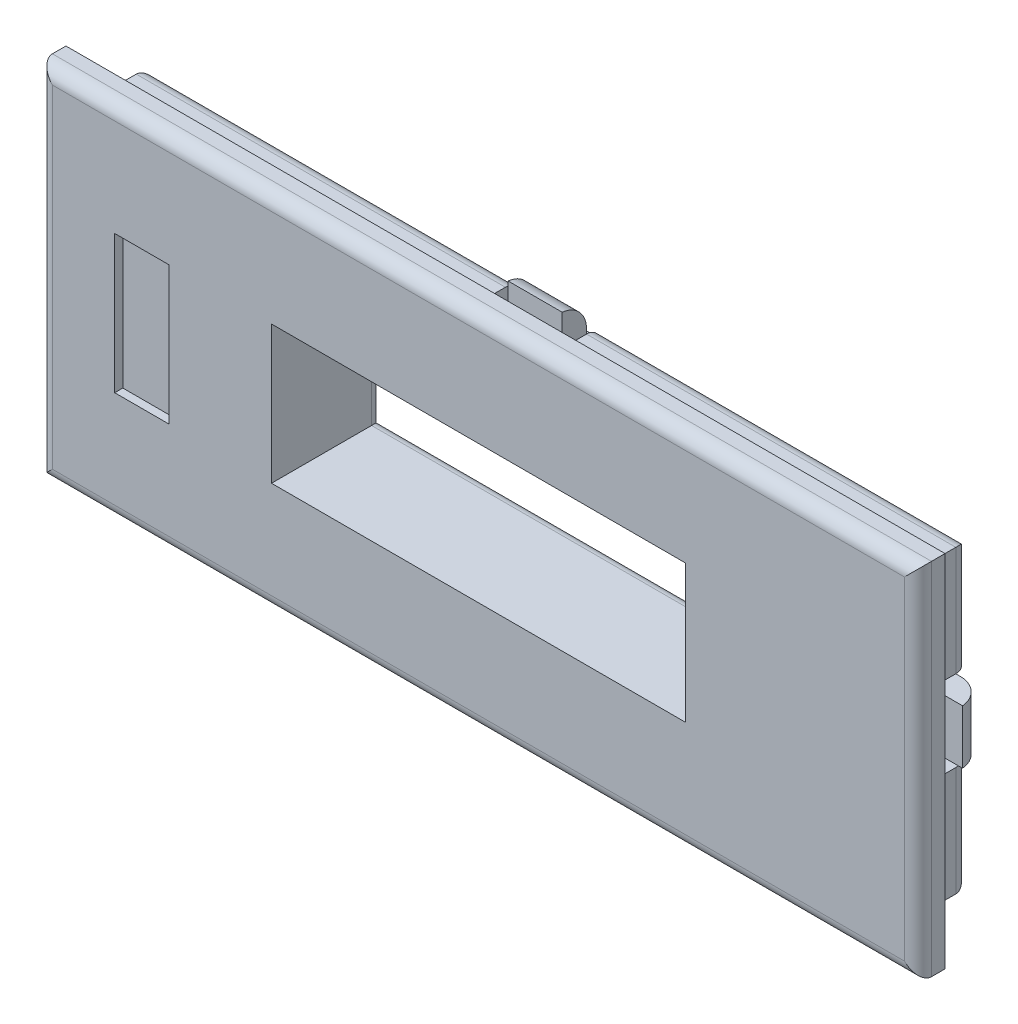
SolidWorks part; units mm, degrees
material "Guma"
ref_plane "Płaszczyzna przednia" through (0, 0, 0) normal (0, 0, 1) x (1, 0, 0)
ref_plane "Płaszczyzna górna" through (0, 0, 0) normal (0, 1, 0) x (1, 0, 0)
ref_plane "Płaszczyzna prawa" through (0, 0, 0) normal (1, 0, 0) x (0, 0, -1)
sketch "Szkic1" plane through (0, 0, 0) normal (0, 0, 1) x (1, 0, 0)
  line L0 (-15.8342, 6.0152) -> (-15.8342, -3.0848)
  line L1 (-16.8298, 7.0152) -> (13.4702, 7.0152)
  line L2 (-16.8298, 7.0152) -> (-16.8298, -4.0848)
  line L3 (-16.8298, -4.0848) -> (13.4702, -4.0848)
  line L4 (13.4702, 7.0152) -> (13.4702, -4.0848)
  line L5 (12.4702, -3.0848) -> (12.4702, 6.0152)
  line L6 (-15.8342, -3.0848) -> (12.4702, -3.0848)
  line L7 (-15.8342, 6.0152) -> (12.4702, 6.0152)
  dimension "D1" = 11.1
  dimension "D2" = 30.3
extrude "Dodanie-wyciągnięcie1" add sketch "Szkic1" along normal blind 2
sketch "Szkic2" plane through (0, 0, 2) normal (0, 0, 1) x (1, 0, 0)
  line L0 (13.4702, 7.0152) -> (-16.8298, 7.0152) construction
  line L1 (-17.9298, 8.1152) -> (14.5702, 8.1152)
  line L2 (-17.9298, 8.1152) -> (-17.9298, -5.1848)
  line L3 (-17.9298, -5.1848) -> (14.5702, -5.1848)
  line L4 (14.5702, 8.1152) -> (14.5702, -5.1848)
  line L5 (-16.8298, 7.0152) -> (-16.8298, -4.0848) construction
  line L6 (13.4702, -4.0848) -> (13.4702, 7.0152) construction
  line L7 (-16.8298, -4.0848) -> (13.4702, -4.0848) construction
  dimension "D1" = 1.1
  dimension "D2" = 1.1
  dimension "D3" = 1.1
  dimension "D4" = 1.1
extrude "Dodanie-wyciągnięcie2" add sketch "Szkic2" along normal blind 1
fillet "Zaokrąglenie1" radius 0.5 4 edges at (-1.6798, 8.1152, 3) (14.5702, 1.4652, 3) (-1.6798, -5.1848, 3) (-17.9298, 1.4652, 3)
sketch "Szkic3" plane through (0, 0, 0) normal (0, 0, -1) x (-1, 0, 0)
  line L4 (16.9298, 2.4652) -> (15.8342, 2.4652)
  line L5 (-13.6702, 0.4652) -> (-12.4702, 0.4652)
  line L6 (2.682, 7.2152) -> (2.682, 6.0152)
  line L7 (0.682, 7.2152) -> (0.682, 6.0152)
  line L8 (-13.6702, 2.9652) -> (-12.4702, 2.9652)
  line L9 (-13.6702, -0.0348) -> (-12.4702, -0.0348)
  line L10 (3.182, -4.1848) -> (3.182, -3.0848)
  line L11 (0.182, 7.2152) -> (0.182, 6.0152)
  line L12 (-13.4702, -4.0848) -> (-13.4702, 7.0152) construction
  line L13 (0.182, 7.2152) -> (0.682, 7.2152)
  line L14 (-13.6702, 2.9652) -> (-13.6702, 2.4652)
  line L15 (0.182, -4.1848) -> (0.682, -4.1848)
  line L16 (16.9298, 2.9652) -> (16.9298, 2.4652)
  line L17 (-13.4702, 7.0152) -> (16.8298, 7.0152) construction
  line L18 (0.182, -3.0848) -> (0.682, -3.0848)
  line L19 (-12.4702, 2.4652) -> (-13.6702, 2.4652)
  line L20 (3.182, -4.1848) -> (2.682, -4.1848)
  line L21 (2.682, -3.0848) -> (3.182, -3.0848)
  line L22 (0.182, -3.0848) -> (0.182, -4.1848)
  line L23 (0.682, -3.0848) -> (0.682, -4.1848)
  line L24 (2.682, -3.0848) -> (2.682, -4.1848)
  line L26 (15.8342, -0.0348) -> (16.9298, -0.0348)
  line L27 (15.8342, 0.4652) -> (16.9298, 0.4652)
  line L29 (15.8342, 2.9652) -> (16.9298, 2.9652)
  line L30 (3.182, 6.0152) -> (3.182, 7.2152)
  line L31 (15.8342, 2.9652) -> (15.8342, 2.4652)
  line L32 (16.9298, 0.4652) -> (16.9298, -0.0348)
  line L33 (15.8342, 0.4652) -> (15.8342, -0.0348)
  line L34 (0.182, 6.0152) -> (0.682, 6.0152)
  line L35 (2.682, 7.2152) -> (3.182, 7.2152)
  line L36 (2.682, 6.0152) -> (3.182, 6.0152)
  line L37 (-12.4702, 2.9652) -> (-12.4702, 2.4652)
  line L38 (-13.6702, 0.4652) -> (-13.6702, -0.0348)
  line L39 (-12.4702, 0.4652) -> (-12.4702, -0.0348)
  dimension "D11" = 0.2
  dimension "D12" = 0.2
extrude "Wytnij-wyciągnięcie1" cut sketch "Szkic3" against normal blind 1.4
fillet "Zaokrąglenie2" radius 0.5 8 edges at (-10.0059, 7.0152, 0) (-16.8298, 4.9902, 0) (-16.8298, -2.0598, 0) (-10.0059, -4.0848, 0) (6.6441, -4.0848, 0) (13.4702, -2.0598, 0) (13.4702, 4.9902, 0) (6.6441, 7.0152, 0)
sketch "Szkic4" plane through (0, 0, 0) normal (0, 0, -1) x (-1, 0, 0)
  line L0 (2.682, 7.0152) -> (2.682, 6.0152) construction
  line L1 (0.682, 6.0152) -> (2.682, 6.0152)
  line L2 (0.682, 6.0152) -> (0.682, 7.1652)
  line L4 (2.682, 6.0152) -> (2.682, 7.1652)
  line L6 (2.682, -3.0848) -> (2.682, -4.0848) construction
  line L7 (0.682, -3.0848) -> (2.682, -3.0848)
  line L8 (0.682, -3.0848) -> (0.682, -4.2348)
  line L9 (0.682, -4.2348) -> (2.682, -4.2348)
  line L10 (2.682, -3.0848) -> (2.682, -4.2348)
  line L11 (2.682, -4.0848) -> (0.682, -4.0848) construction
  line L12 (15.8342, 2.4652) -> (15.8342, 0.4652) construction
  line L13 (15.8342, 2.4652) -> (16.9798, 2.4652)
  line L14 (15.8342, 2.4652) -> (15.8342, 0.4652)
  line L15 (15.8342, 0.4652) -> (16.9798, 0.4652)
  line L16 (16.9798, 2.4652) -> (16.9798, 0.4652)
  line L17 (16.8298, 0.4652) -> (15.8342, 0.4652) construction
  line L18 (16.8298, 2.4652) -> (16.8298, 0.4652) construction
  line L19 (-13.4702, 2.4652) -> (-12.4702, 2.4652) construction
  line L20 (-12.4702, 0.4652) -> (-13.6202, 0.4652)
  line L21 (-12.4702, 0.4652) -> (-12.4702, 2.4652)
  line L22 (-12.4702, 2.4652) -> (-13.6202, 2.4652)
  line L23 (-13.6202, 0.4652) -> (-13.6202, 2.4652)
  line L24 (-13.4702, 0.4652) -> (-13.4702, 2.4652) construction
  line L25 (0.682, 7.1652) -> (0.682, 7.6652)
  line L26 (0.682, 7.6652) -> (2.682, 7.6652)
  line L27 (2.682, 7.6652) -> (2.682, 7.1652)
  dimension "D1" = 0
  dimension "D3" = 0
  dimension "D4" = 0.15
  dimension "D5" = 0
  dimension "D6" = 0.15
  dimension "D7" = 0
  dimension "D8" = 0.15
  dimension "D9" = 0.5
extrude "Dodanie-wyciągnięcie3" add sketch "Szkic4" against normal blind 0.9
sketch "Szkic5" plane through (13.6202, 0, 0) normal (1, 0, 0) x (0, 0, -1)
  line L1 (-0.9, 2.4652) -> (0, 2.4652)
  line L2 (-0.9, 2.4652) -> (-0.9, 0.4652)
  line L3 (-0.9, 0.4652) -> (0, 0.4652)
  line L4 (0, 2.4652) -> (0, 0.4652)
extrude "Dodanie-wyciągnięcie4" add sketch "Szkic5" along normal blind 0.5
sketch "Szkic6" plane through (0, -4.2348, 0) normal (0, -1, 0) x (1, 0, 0)
  line L1 (-0.682, 0) -> (-2.682, 0)
  line L2 (-0.682, 0) -> (-0.682, 0.9)
  line L3 (-0.682, 0.9) -> (-2.682, 0.9)
  line L4 (-2.682, 0) -> (-2.682, 0.9)
extrude "Dodanie-wyciągnięcie5" add sketch "Szkic6" along normal blind 0.5
sketch "Szkic7" plane through (-16.9798, 0, 0) normal (-1, 0, 0) x (0, 0, 1)
  line L1 (0.9, 0.4652) -> (0, 0.4652)
  line L2 (0.9, 0.4652) -> (0.9, 2.4652)
  line L3 (0.9, 2.4652) -> (0, 2.4652)
  line L4 (0, 0.4652) -> (0, 2.4652)
extrude "Dodanie-wyciągnięcie6" add sketch "Szkic7" along normal blind 0.5
fillet "Zaokrąglenie5" radius 1 4 edges at (-1.682, 7.6652, 0) (14.1202, 1.4652, 0) (-1.682, -4.7348, 0) (-17.4798, 1.4652, 0)
sketch "Szkic8" plane through (0, 0, 2) normal (0, 0, -1) x (-1, 0, 0)
  line L1 (-12.4702, 6.0152) -> (15.8342, 6.0152)
  line L2 (-12.4702, 6.0152) -> (-12.4702, -3.0848)
  line L3 (-12.4702, -3.0848) -> (15.8342, -3.0848)
  line L4 (15.8342, 6.0152) -> (15.8342, -3.0848)
extrude "Dodanie-wyciągnięcie7" add sketch "Szkic8" along normal up to vertex (0.6 mm away) up to point (-15.8342, 0.4652, 1.4)
sketch "Szkic9" plane through (0, 0, 3) normal (0, 0, 1) x (1, 0, 0)
  line L0 (-17.4298, 1.4652) -> (14.0702, 1.4652) construction
  line L1 (-1.6798, 7.6152) -> (-1.6798, -4.6848) construction
  line L2 (-9.3298, -1.0848) -> (-9.3298, 4.0152)
  line L3 (5.9702, -1.0848) -> (-9.3298, -1.0848)
  line L4 (5.9702, 4.0152) -> (-9.3298, 4.0152)
  line L6 (5.9702, 4.0152) -> (5.9702, -1.0848)
extrude "Wytnij-wyciągnięcie2" cut sketch "Szkic9" against normal up to surface (1.6 mm away) up to face at (-1.6815, 1.4652, 1.4)
sketch "Szkic10" plane through (0, 0, 1.4) normal (0, 0, -1) x (-1, 0, 0)
  line L0 (-7.4702, 5.5152) -> (10.8298, 5.5152)
  line L1 (-5.9702, 4.0152) -> (9.3298, 4.0152)
  line L2 (-5.9702, 4.0152) -> (-5.9702, -1.0848)
  line L3 (-5.9702, -1.0848) -> (9.3298, -1.0848)
  line L4 (9.3298, 4.0152) -> (9.3298, -1.0848)
  line L9 (-7.4702, -2.5848) -> (-7.4702, 5.5152)
  line L10 (10.8298, -2.5848) -> (10.8298, 5.5152)
  line L11 (-5.9702, -2.5848) -> (9.3298, -2.5848)
  line L12 (9.3298, -2.5848) -> (10.8298, -2.5848)
  line L13 (-5.9702, -2.5848) -> (-7.4702, -2.5848)
  circle A0 centre (-5.9702, 4.0152) radius 1.5 construction
  circle A1 centre (-5.9702, -1.0848) radius 1.5 construction
  circle A2 centre (9.3298, 4.0152) radius 1.5 construction
  circle A3 centre (9.3298, -1.0848) radius 1.5 construction
extrude "Dodanie-wyciągnięcie8" add sketch "Szkic10" along normal blind 2.5
fillet "Zaokrąglenie6" radius 0.4 4 edges at (5.9702, 1.4652, -1.1) (-1.6798, -1.0848, -1.1) (-9.3298, 1.4652, -1.1) (-1.6798, 4.0152, -1.1)
sketch "Szkic11" plane through (0, 0, 3) normal (0, 0, 1) x (1, 0, 0)
  line L0 (-9.3298, 4.0152) -> (-17.4298, 4.0152) construction
  line L1 (-13.1271, 7.6152) -> (-13.1271, -4.6848) construction
  line L2 (-11.3755, 7.6152) -> (-15.6573, 7.6152) construction
  line L3 (-9.3298, -1.0848) -> (-17.4298, -1.0848) construction
  line L5 (-13.1271, 4.0152) -> (-15.1271, 4.0152)
  line L6 (-13.1271, 4.0152) -> (-13.1271, -1.0848)
  line L7 (-13.1271, -1.0848) -> (-15.1271, -1.0848)
  line L8 (-15.1271, 4.0152) -> (-15.1271, -1.0848)
  dimension "D1" = 2
  dimension "D2" = 0
extrude "Wytnij-wyciągnięcie3" cut sketch "Szkic11" against normal blind 0.3
